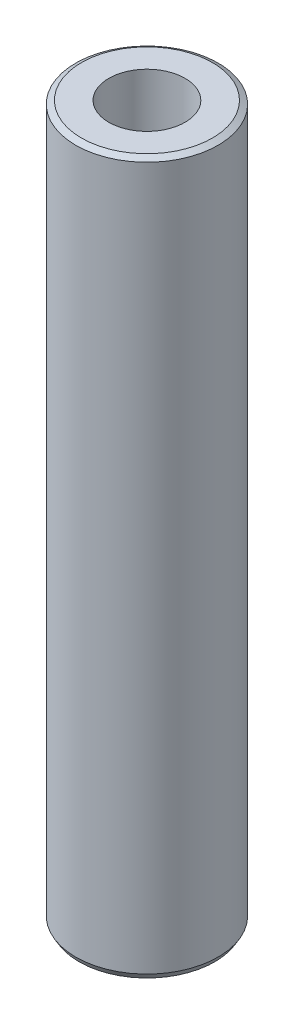
SolidWorks part; units mm, degrees
ref_plane "Front Plane" through (0, 0, 0) normal (0, 0, 1) x (1, 0, 0)
ref_plane "Top Plane" through (0, 0, 0) normal (0, 1, 0) x (1, 0, 0)
ref_plane "Right Plane" through (0, 0, 0) normal (1, 0, 0) x (0, 0, -1)
sketch "Sketch1" plane through (0, 0, 0) normal (0, 1, 0) x (1, 0, 0)
  circle A0 centre (0, 0) radius 60
  dimension "SHAFT_OD" = 120
extrude "Boss-Extrude1" add sketch "Sketch1" along normal blind 600
sketch "Sketch2" plane through (0, 0, 0) normal (0, 1, 0) x (1, 0, 0)
  circle A0 centre (0, 0) radius 32.1249
  dimension "BORE_D" = 64.2497
extrude "Cut-Extrude1" cut sketch "Sketch2" along normal through all
chamfer "Chamfer1" distance 2.8046 angle 60 2 edges at (0, 600, 60) (0, 0, 60) first distance on face at (0, 600, 60) first distance on face at (0, 0, 32.1249)
